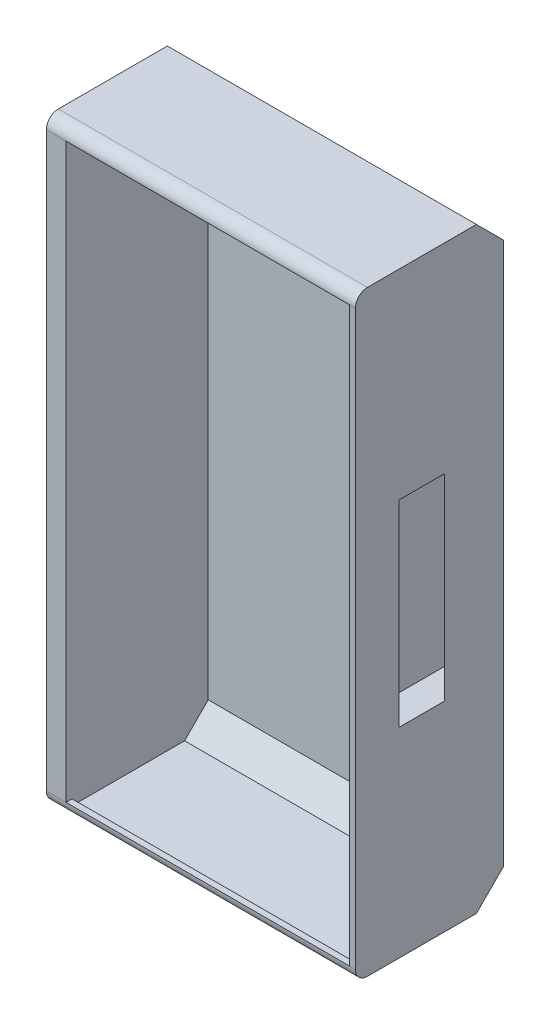
SolidWorks part; units mm, degrees
ref_plane "Front Plane" through (0, 0, 0) normal (1, 0, 0) x (0, 1, 0)
ref_plane "Top Plane" through (0, 0, 0) normal (0, 0, 1) x (0, 1, 0)
ref_plane "Right Plane" through (0, 0, 0) normal (0, 1, 0) x (-1, 0, 0)
sketch "Sketch1" plane through (0, 0, 0) normal (1, 0, 0) x (0, 1, 0)
  line L12 (-98.46, -46.9834) -> (-89.4834, -55.96)
  line L13 (-89.4834, -55.96) -> (89.4834, -55.96)
  line L14 (89.4834, -55.96) -> (98.46, -46.9834)
  line L15 (98.46, -46.9834) -> (98.46, -11)
  line L16 (94.5, -7.04) -> (-94.5, -7.04)
  line L17 (-98.46, -11) -> (-98.46, -46.9834)
  line L18 (-98.46, -46.9834) -> (-89.4834, -55.96)
  line L19 (-89.4834, -55.96) -> (89.4834, -55.96)
  line L20 (89.4834, -55.96) -> (98.46, -46.9834)
  line L21 (98.46, -46.9834) -> (98.46, -11)
  line L22 (94.5, -7.04) -> (-94.5, -7.04)
  line L23 (-98.46, -11) -> (-98.46, -46.9834)
  arc A4 (98.46, -11) -> (94.5, -7.04) centre (94.5, -11) ccw
  arc A5 (-94.5, -7.04) -> (-98.46, -11) centre (-94.5, -11) ccw
  arc A6 (98.46, -11) -> (94.5, -7.04) centre (94.5, -11) ccw
  arc A7 (-94.5, -7.04) -> (-98.46, -11) centre (-94.5, -11) ccw
  dimension "D1" = 0.04
extrude "Boss-Extrude1" add sketch "Sketch1" along normal up to surface (102 mm away) contours L18 L19 L20 L21 A6 L22 A7 L23
ref_plane "Plane3" through (0, 0, 0) normal (0, 1, 0) x (1, 0, 0)
sketch "Sketch11" plane through (0, 0, 0) normal (0, 1, 0) x (1, 0, 0)
  line L0 (102, 28.9917) -> (104.8284, 26.1633)
  line L1 (102, 11) -> (102, 46.9834) construction
  line L2 (102, 28.9917) -> (92.1005, 38.8912)
  dimension "D1" = 14
  dimension "D2" = 4
  dimension "D3" = 45
sketch "Sketch12" plane through (102, 0, 0) normal (1, 0, 0) x (0, 1, 0)
  line L0 (0, -28.9917) -> (0, -26.1633) construction
  line L1 (-32.5, -36.4917) -> (32.5, -36.4917)
  line L2 (-32.5, -36.4917) -> (-32.5, -21.4917)
  line L3 (-32.5, -21.4917) -> (32.5, -21.4917)
  line L4 (32.5, -36.4917) -> (32.5, -21.4917)
  line L5 (-32.5, -36.4917) -> (32.5, -21.4917) construction
  line L6 (-32.5, -21.4917) -> (32.5, -36.4917) construction
  line L7 (0, -28.9917) -> (0, -38.8912) construction
  line L10 (89.4834, -55.96) -> (-89.4834, -55.96) construction
  point P0 (0, -28.9917)
  point P9 (0, 0)
  dimension "D1" = 65
  dimension "D2" = 15
  dimension "D3" = 26.9683
sweep "Cut-Sweep1" cut profiles "Sketch12" path "Sketch11"
shell "Shell1" thickness 2 removed face at (51, 0, -7.04)
sketch "Sketch8" plane through (2, 0, 0) normal (1, 0, 0) x (0, 1, 0)
  line L11 (-10, -31.5) -> (-10, -21.5)
  line L12 (-10, -21.5) -> (10, -21.5)
  line L13 (10, -31.5) -> (10, -21.5)
  line L15 (-98.46, -46.9834) -> (-89.4834, -55.96)
  line L16 (-89.4834, -55.96) -> (89.4834, -55.96)
  line L17 (89.4834, -55.96) -> (98.46, -46.9834)
  line L18 (98.46, -46.9834) -> (98.46, -11)
  line L19 (94.5, -7.04) -> (-94.5, -7.04)
  line L20 (-98.46, -11) -> (-98.46, -46.9834)
  line L21 (-98.46, -46.9834) -> (-89.4834, -55.96)
  line L22 (-89.4834, -55.96) -> (89.4834, -55.96)
  line L23 (89.4834, -55.96) -> (98.46, -46.9834)
  line L24 (98.46, -46.9834) -> (98.46, -11)
  line L25 (94.5, -7.04) -> (-94.5, -7.04)
  line L26 (-98.46, -11) -> (-98.46, -46.9834)
  arc A0 (-10, -31.5) -> (10, -31.5) centre (0, -31.5) ccw
  arc A5 (98.46, -11) -> (94.5, -7.04) centre (94.5, -11) ccw
  arc A6 (-94.5, -7.04) -> (-98.46, -11) centre (-94.5, -11) ccw
  arc A7 (98.46, -11) -> (94.5, -7.04) centre (94.5, -11) ccw
  arc A8 (-94.5, -7.04) -> (-98.46, -11) centre (-94.5, -11) ccw
  point P4 (0, -55.96)
  dimension "D2" = 20
  dimension "D3" = 24.46
  dimension "D4" = 10
  dimension "D5" = 20
  dimension "D1" = 0
extrude "Boss-Extrude2" add sketch "Sketch8" along normal blind 2.5
sketch "Sketch10" plane through (4.5, 0, 0) normal (1, 0, 0) x (0, 1, 0)
  line L8 (94.5, -9.04) -> (94.5, -7.04)
  line L9 (94.5, -7.04) -> (-94.5, -7.04)
  line L10 (-94.5, -7.04) -> (-94.5, -9.04)
  line L11 (-96.46, -11) -> (-96.46, -46.155)
  line L12 (-96.46, -46.155) -> (-88.655, -53.96)
  line L13 (-88.655, -53.96) -> (88.655, -53.96)
  line L14 (88.655, -53.96) -> (96.46, -46.155)
  line L15 (96.46, -46.155) -> (96.46, -11)
  line L16 (94.5, -9.04) -> (94.5, -7.04)
  line L17 (94.5, -7.04) -> (-94.5, -7.04)
  line L18 (-94.5, -7.04) -> (-94.5, -9.04)
  line L19 (-96.46, -11) -> (-96.46, -46.155)
  line L20 (-96.46, -46.155) -> (-88.655, -53.96)
  line L21 (-88.655, -53.96) -> (88.655, -53.96)
  line L22 (88.655, -53.96) -> (96.46, -46.155)
  line L23 (96.46, -46.155) -> (96.46, -11)
  arc A2 (-94.5, -9.04) -> (-96.46, -11) centre (-94.5, -11) ccw
  arc A3 (96.46, -11) -> (94.5, -9.04) centre (94.5, -11) ccw
  arc A4 (-94.5, -9.04) -> (-96.46, -11) centre (-94.5, -11) ccw
  arc A5 (96.46, -11) -> (94.5, -9.04) centre (94.5, -11) ccw
  dimension "D1" = 0
extrude "Boss-Extrude3" add sketch "Sketch10" along normal blind 2
chamfer "Chamfer1" distance 20 angle 45 1 edges at (100, 0, -41.3201) first distance on face at (100, 0, -25.3578)
